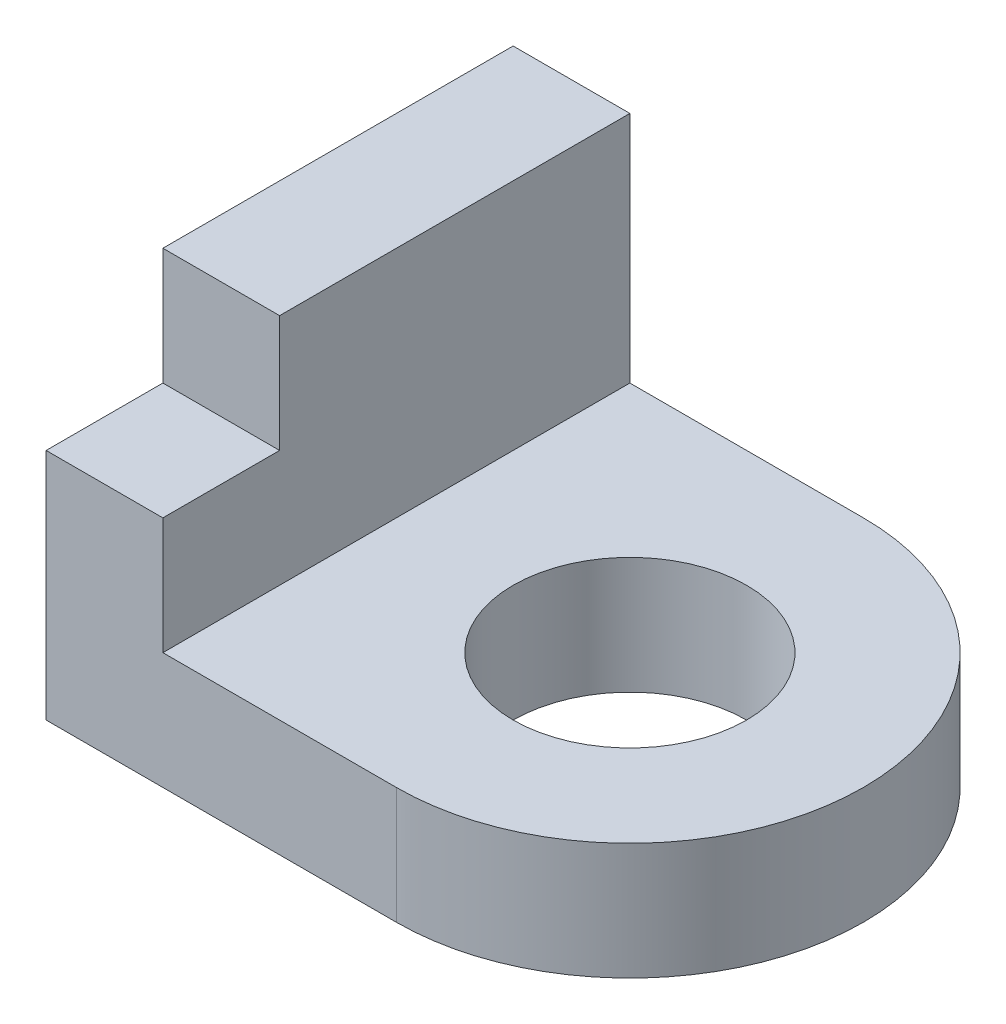
SolidWorks part; units mm, degrees
ref_plane "前基準面" through (0, 0, 0) normal (0, 0, 1) x (1, 0, 0)
ref_plane "上基準面" through (0, 0, 0) normal (0, 1, 0) x (1, 0, 0)
ref_plane "右基準面" through (0, 0, 0) normal (1, 0, 0) x (0, 0, -1)
sketch "草圖1" plane through (0, 0, 0) normal (0, 1, 0) x (1, 0, 0)
  line L1 (0, 10) -> (-15, 10)
  line L3 (0, -10) -> (-15, -10)
  line L4 (-15, 10) -> (-15, -10)
  line L5 (-15, 10) -> (-10, 10)
  line L6 (-15, 10) -> (-15, -5)
  line L7 (-15, -5) -> (-10, -5)
  line L8 (-10, 10) -> (-10, -5)
  line L9 (-15, -10) -> (-10, -10)
  line L10 (-15, -10) -> (-15, -5)
  line L11 (-15, -5) -> (-10, -5)
  line L12 (-10, -10) -> (-10, -5)
  circle A0 centre (0, 0) radius 5
  arc A1 (0, -10) -> (0, 10) centre (0, 0) ccw
  dimension "D1" = 20
  dimension "D2" = 10
  dimension "D4" = 5
  dimension "D5" = 5
extrude "填料-伸長1" add sketch "草圖1" along normal blind 5 contours L3 A1 L1 L8 L12 A0 region at (9.7172, 0, 0)
extrude "填料-伸長2" add sketch "草圖1<3>" along normal blind 10 contours L3 L12 L7 L4 region at (-12.5, 0, 7.5)
sketch "草圖1<3>" plane through (0, 0, 0) normal (0, 1, 0) x (1, 0, 0) same geometry as "草圖1"
extrude "填料-伸長3" add sketch "草圖1<4>" along normal blind 15 contours L8 L1 L4 L7 region at (-12.5, 0, -2.5)
sketch "草圖1<4>" plane through (0, 0, 0) normal (0, 1, 0) x (1, 0, 0) same geometry as "草圖1"
